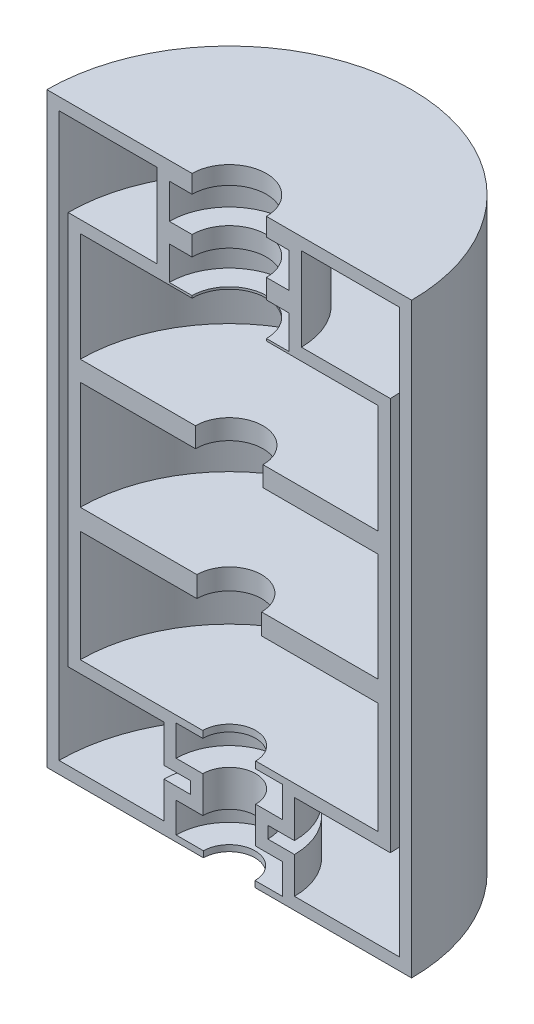
SolidWorks part; units mm, degrees
material "6061-T6 (SS)"
ref_plane "Front" through (0, 0, 0) normal (0, 0, 1) x (1, 0, 0)
ref_plane "Top" through (0, 0, 0) normal (0, 1, 0) x (1, 0, 0)
ref_plane "Right" through (0, 0, 0) normal (1, 0, 0) x (0, 0, -1)
sketch "Sketch1" plane through (0, 0, 0) normal (0, 0, 1) x (1, 0, 0)
  line L0 (12.7, -245.1583) -> (12.7, -242.1389)
  line L1 (12.7, -245.2687) -> (12.7, -190.6587) construction
  line L2 (12.7, -242.1389) -> (26.1633, -242.1389)
  line L3 (26.1633, -242.1389) -> (26.1633, -227.2882)
  line L4 (26.1633, -227.2882) -> (13.0385, -227.2882)
  line L5 (13.0385, -227.2882) -> (13.0385, -209.3958)
  line L6 (13.0385, -209.3958) -> (26.1633, -209.3958)
  line L7 (26.1633, -209.3958) -> (26.1633, -194.3223)
  line L8 (26.1633, -194.3223) -> (13.0385, -194.3223)
  line L9 (13.0385, -194.3223) -> (13.0385, -190.9517)
  line L10 (13.0385, -190.9517) -> (73.4027, -190.9517)
  line L11 (73.4027, -190.9517) -> (73.4027, -136.1203)
  line L12 (73.4027, -136.1203) -> (15.9244, -136.1203)
  line L13 (15.9244, -136.1203) -> (15.9244, -125.8731)
  line L14 (15.9244, -125.8731) -> (73.4027, -125.8731)
  line L15 (73.4027, -125.8731) -> (73.4027, -72.5019)
  line L16 (73.4027, -72.5019) -> (16.6402, -72.5019)
  line L17 (16.6402, -72.5019) -> (16.6402, -62.6816)
  line L18 (16.6402, -62.6816) -> (73.4027, -62.6816)
  line L19 (73.4027, -62.6816) -> (73.4027, -9.0581)
  line L20 (73.4027, -9.0581) -> (18.3121, -9.0581)
  line L21 (18.3121, -9.0581) -> (18.3121, -7.977)
  line L22 (18.3121, -7.977) -> (29.5515, -7.977)
  line L23 (29.5515, -7.977) -> (29.5515, 8.4803)
  line L24 (29.5515, 8.4803) -> (18.3121, 8.4803)
  line L25 (18.3121, 8.4803) -> (18.3121, 18.0905)
  line L26 (18.3121, 18.0905) -> (29.5515, 18.0905)
  line L27 (29.5515, 18.0905) -> (29.5515, 35.2685)
  line L28 (29.5515, 35.2685) -> (18.3121, 35.2685)
  line L29 (18.3121, 35.2685) -> (18.3121, 44.1579)
  line L30 (18.3121, 44.1579) -> (89.8744, 44.1579)
  line L31 (89.8744, 44.1579) -> (89.8744, -245.1583)
  line L32 (89.8744, -245.1583) -> (12.7, -245.1583)
  line L33 (0, 19.8437) -> (0, 34.1312) construction
  line L34 (0, 19.8437) -> (0, 34.1312)
  point P13 (12.7, -245.1583)
  point P36 (13.0385, -245.1583)
revolve "Revolve1" add sketch "Sketch1" angle 180 about L34 region at (15.6943, -243.6486, 0)
shell "Shell1" thickness 6 removed face at (-34.2369, -101.0919, 0) removed face at (34.2369, -101.0919, 0)
